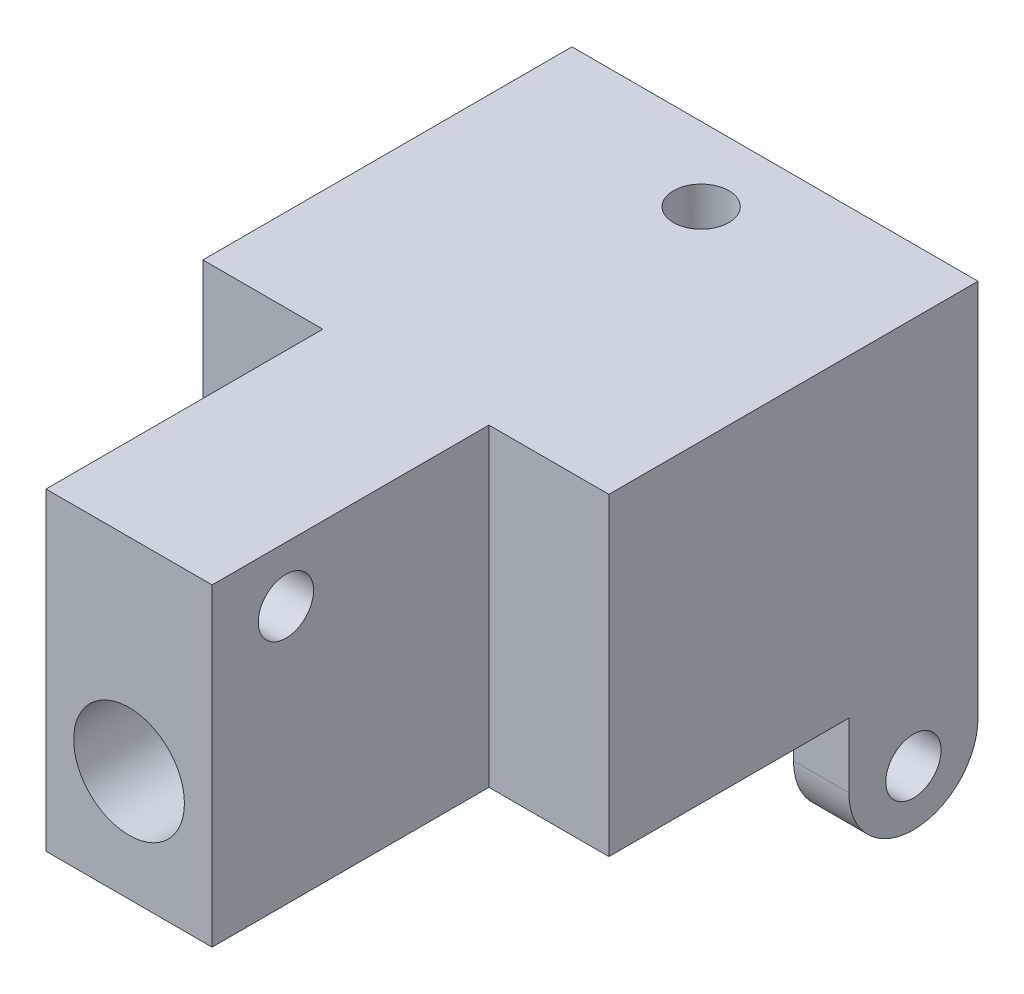
SolidWorks part; units mm, degrees
ref_plane "Płaszczyzna przednia" through (0, 0, 0) normal (0, 0, 1) x (1, 0, 0)
ref_plane "Płaszczyzna górna" through (0, 0, 0) normal (0, 1, 0) x (1, 0, 0)
ref_plane "Płaszczyzna prawa" through (0, 0, 0) normal (1, 0, 0) x (0, 0, -1)
sketch "Szkic1" plane through (0, 0, 0) normal (0, 0, 1) x (1, 0, 0)
  line L1 (8, 6) -> (-8, 6)
  line L3 (8, -6) -> (-8, -6)
  line L5 (8, 6) -> (-8, -6) construction
  line L6 (8, -6) -> (-8, 6) construction
  line L7 (8, 6) -> (11, 6)
  line L8 (8, -6) -> (8, -13)
  line L9 (8, -13) -> (11, -13)
  line L10 (11, 6) -> (11, -13)
  line L11 (-8, 6) -> (-11, 6)
  line L12 (-8, -6) -> (-8, -13)
  line L13 (-8, -13) -> (-11, -13)
  line L14 (-11, 6) -> (-11, -13)
  point P0 (0, 0)
  dimension "D1" = 16
  dimension "D2" = 12
  dimension "D3" = 7
  dimension "D4" = 7
  dimension "D5" = 3
  dimension "D6" = 3
extrude "Dodanie-wyciągnięcie1" add sketch "Szkic1" along normal blind 7
sketch "Szkic2" plane through (-11, 0, 0) normal (-1, 0, 0) x (0, 0, 1)
  line L0 (7, -13) -> (0, -13) construction
  line L1 (0, -9.5) -> (0, -13)
  line L2 (0, -13) -> (7, -13)
  line L3 (7, -13) -> (7, -9.5)
  arc A0 (0, -9.5) -> (7, -9.5) centre (3.5, -9.5) ccw
  line M1 (0, 6) -> (0, -13)
  line M2 (0, -13) -> (7, -13)
  line M3 (7, -13) -> (7, 6)
  dimension "D1" = 7
  dimension "D2" = 3.5
extrude "Wytnij-wyciągnięcie1" cut sketch "Szkic2" against normal up to surface (22 mm away) contours A0 L2 M3 | A0 M1 M2 region at (-11, -12.2182, 0.7818) region at (-11, -12.2182, 6.2182) up to face at (11, -3.5, 3.5)
sketch "Szkic3" plane through (-11, 0, 0) normal (-1, 0, 0) x (0, 0, 1)
  line L0 (3.5, 6) -> (3.5, -13.7155) construction
  line L1 (7, 6) -> (0, 6) construction
  circle A0 centre (3.5, -10) radius 1.5
  arc A2 (0, -9.5) -> (7, -9.5) centre (3.5, -9.5) ccw construction
  dimension "D1" = 3
  dimension "D2" = 3
extrude "Wytnij-wyciągnięcie2" cut sketch "Szkic3" against normal up to surface (22 mm away) up to face at (11, -2.625, 3.5)
sketch "Szkic4" plane through (0, 0, 0) normal (0, 0, -1) x (-1, 0, 0)
  line L0 (8, -6) -> (11, -6) construction
  line L1 (11, 6) -> (11, -9.5) construction
  line L2 (-11, 6) -> (-11, 11.4053) construction
  line L3 (-11, 6) -> (11, 6) construction
  line L4 (11, -6) -> (-11, -6)
  line L5 (11, -6) -> (11, 11)
  line L6 (11, 11) -> (-11, 11)
  line L7 (-11, -6) -> (-11, 11)
  dimension "D1" = 5
extrude "Dodanie-wyciągnięcie2" add sketch "Szkic4" against normal blind 20 contours L6 L7 L4 L5
sketch "Szkic5" plane through (0, 0, 20) normal (0, 0, 1) x (1, 0, 0)
  circle A0 centre (0, 0) radius 3
  dimension "D1" = 6
extrude "Wytnij-wyciągnięcie3" cut sketch "Szkic5" against normal up to surface (20 mm away) up to face at (0, -3.5, 0)
ref_plane "Płaszczyzna4" through (0, 4, 0) normal (0, 1, 0) x (1, 0, 0)
sketch "Szkic6" plane through (0, 4, 0) normal (0, -1, 0) x (-1, 0, 0)
  line L0 (0, 0) -> (0, -0.7869) construction
  line L1 (2.65, -2.3168) -> (2.65, 0)
  line L2 (-2.65, -5.3768) -> (0, -6.9068)
  line L3 (0, -6.9068) -> (2.65, -5.3768)
  line L4 (2.65, -5.3768) -> (2.65, -2.3168)
  line L7 (-2.65, -2.3168) -> (-2.65, -5.3768)
  line L8 (3, 0) -> (-3, 0) construction
  line L9 (2.65, 0) -> (-2.65, 0)
  line L10 (-2.65, 0) -> (-2.65, -2.3168)
  line L11 (0, -1.1968) -> (0, -10.3286) construction
  line L12 (2.65, -2.3168) -> (1.325, -1.5519) [skipped]
  line L13 (-1.325, -1.5519) -> (-2.65, -2.3168) [skipped]
  circle A0 centre (0, -3.8468) radius 2.65 construction
  dimension "D1" = 5.3
extrude "Wytnij-wyciągnięcie4" cut sketch "Szkic6" against normal blind 2.5
sketch "Szkic7" plane through (0, 4, 0) normal (0, 1, 0) x (1, 0, 0)
  line L5 (-2.65, 0) -> (2.65, 0) construction
  circle A0 centre (0, -4) radius 1.5
  dimension "D1" = 3
  dimension "D2" = 4
extrude "Wytnij-wyciągnięcie5" cut sketch "Szkic7" against normal up to surface and the other way up to surface (7 mm away) up to face at (3, 0, 20) other way up to face at (0, 11, 10)
sketch "Szkic8" plane through (0, 0, 20) normal (0, 0, 1) x (1, 0, 0)
  line L0 (-11, -6) -> (11, -6) construction
  line L1 (-4.5, -6) -> (4.5, -6)
  line L2 (-4.5, -6) -> (-4.5, 11)
  line L3 (-4.5, 11) -> (4.5, 11)
  line L4 (4.5, -6) -> (4.5, 11)
  line L5 (-11, 11) -> (11, 11) construction
  circle A0 centre (0, 0) radius 3
  circle A1 centre (0, 0) radius 3
  circle M3 centre (0, 0) radius 3
  line M5 (-11, -6) -> (11, -6)
  line M7 (11, 11) -> (-11, 11)
  dimension "D1" = 9
  dimension "D2" = 4.5
extrude "Dodanie-wyciągnięcie3" add sketch "Szkic8" along normal blind 15 contours L4 L2 M5 M7 M3 region at (0, 3.0667, 20)
sketch "Szkic9" plane through (4.5, 0, 0) normal (1, 0, 0) x (0, 0, -1)
  line L0 (-35, 11) -> (-20, 11) construction
  line L2 (-35, -6) -> (-35, 11) construction
  circle A0 centre (-31, 8) radius 1.5
  dimension "D1" = 3
  dimension "D2" = 3
  dimension "D3" = 4
extrude "Wytnij-wyciągnięcie6" cut sketch "Szkic9" against normal up to surface (9 mm away) up to face at (-4.5, 2.5, 27.5)
